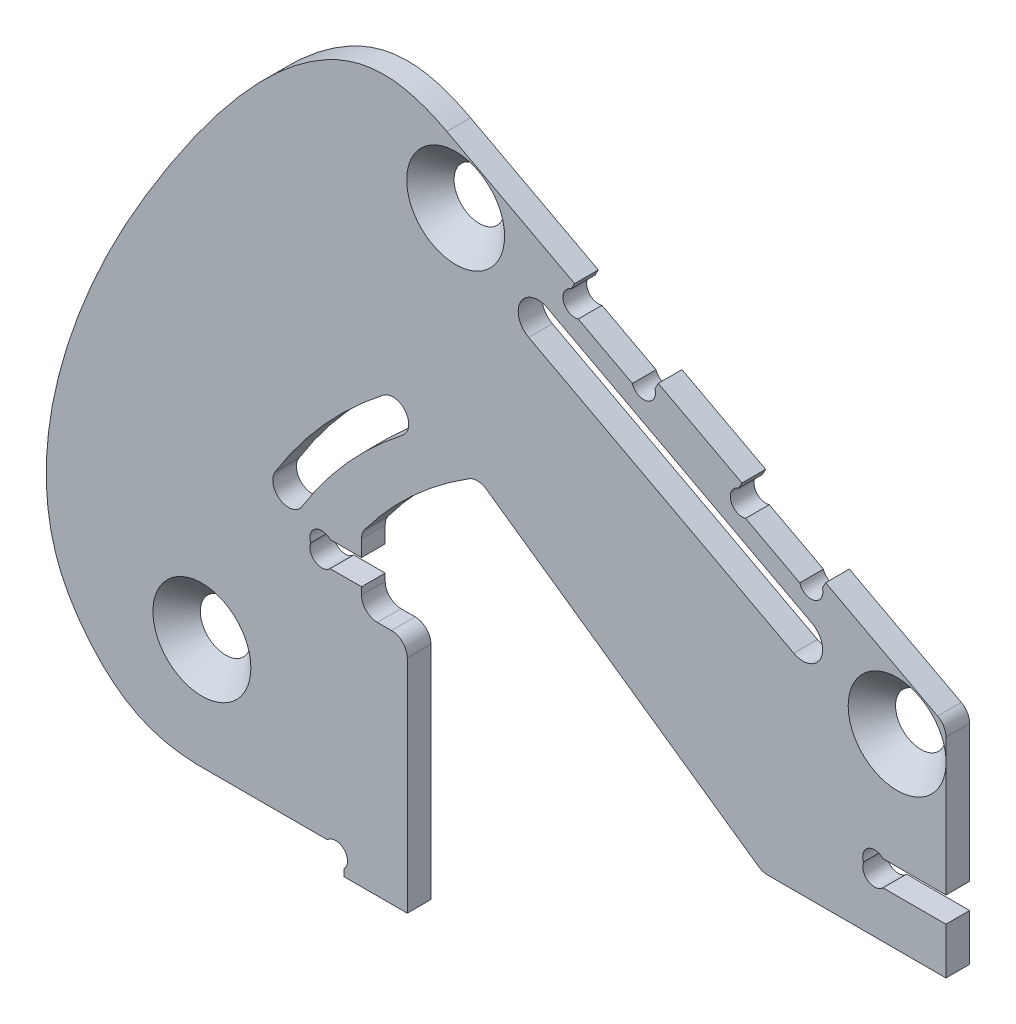
SolidWorks part; units mm, degrees
ref_plane "Front Plane" through (0, 0, 0) normal (0, 0, 1) x (1, 0, 0)
ref_plane "Top Plane" through (0, 0, 0) normal (0, 1, 0) x (1, 0, 0)
ref_plane "Right Plane" through (0, 0, 0) normal (1, 0, 0) x (0, 0, -1)
sketch "Sketch1" plane through (0, 0, 0) normal (0, 0, 1) x (1, 0, 0)
  line L0 (0, 0) -> (-32, 0)
  line L2 (0, 0) -> (2.5, 0)
  line L3 (-1.5, 0) -> (2.5, 0)
  line L4 (-1.5, 0) -> (-1.5, -1.5)
  line L5 (2.5, 0) -> (2.5, 12)
  line L6 (-1.5, -1.5) -> (2.5, -1.5)
  line L7 (-6.1791, 48.5621) -> (62.5843, 12)
  line L8 (62.5843, 12) -> (2.5, 12)
  line L9 (-6.1791, 48.5621) -> (62.5843, 12)
  line L10 (-32, 0) -> (-6.1791, 48.5621)
  line L11 (2.5, 0) -> (2.5, -1.5)
  line L12 (-1.5, 0) -> (2.5, -1.5) construction
  line L13 (-1.5, -1.5) -> (2.5, 0) construction
  point P13 (0.5, -0.75)
  dimension "D1" = 12
  dimension "D2" = 28
  dimension "D3" = 55
  dimension "D4" = 0.5
  dimension "D5" = 32
  dimension "D6" = 4
  dimension "D7" = 1.5
extrude "Base" add sketch "Sketch1" along normal blind 1.5
sketch "Sketch3" plane through (0, 0, 1.5) normal (0, 0, 1) x (1, 0, 0)
  line L0 (62.5843, 12) -> (2.5, 12) construction
  line L1 (25, 12) -> (-3.5, 12)
  line L2 (-0.3961, 13.5) -> (2.5, 13.5)
  line L3 (2.5, 13.5) -> (2.5, 12)
  line L4 (6.9787, 24.6187) -> (25, 12)
  line L5 (2.5, -1.5) -> (2.5, 12) construction
  line L6 (-0.3961, 15) -> (-0.3961, 16.5) construction
  line L7 (-0.3961, 12) -> (-0.3961, 17.9078)
  arc A0 (-3.5, 12) -> (6.9787, 24.6187) centre (19.0917, 3.8998) cw
  point P7 (2.6479, 13.8931)
  line M28 (2.5, 12) -> (62.5843, 12)
  dimension "D3" = 24
  dimension "D1" = 22
  dimension "D2" = 35
  dimension "D4" = 1.5
  dimension "D6" = 28.5
  dimension "D7" = 6
extrude "Camera cut" cut sketch "Sketch3" against normal up to next contours A0 L7 L1 L4 M28
sketch "Sketch4" plane through (0, 0, 1.5) normal (0, 0, 1) x (1, 0, 0)
  line L0 (36.6039, 15) -> (36.6039, 25.814)
  line L1 (-0.3961, 13.5) -> (-0.3961, 17.9078) construction
  line L2 (-6.1791, 48.5621) -> (62.5843, 12) construction
  line L3 (36.6039, 25.814) -> (62.5843, 12)
  line L4 (36.6039, 15) -> (36.6039, 12)
  line L5 (55.3501, 15) -> (1.5, 15) construction
  line L6 (36.6039, 16.5) -> (31.6039, 16.5)
  line L9 (31.6039, 16.5) -> (31.6039, 15)
  line L10 (1.5, 15) -> (-3.5, 15) construction
  line L11 (62.5843, 12) -> (25, 12) construction
  line L12 (31.6039, 15) -> (36.6039, 15)
  line L13 (36.6039, 12) -> (62.5843, 12)
  line L14 (36.6039, 16.55) -> (31.5539, 16.55)
  line L15 (31.5539, 16.55) -> (31.5539, 14.95)
  line L16 (31.5539, 14.95) -> (36.6039, 14.95)
  line L17 (-3.4461, 16.55) -> (-0.3461, 16.55)
  line L18 (-3.3961, 16.5) -> (-0.3961, 16.5)
  line L19 (-3.3961, 16.5) -> (-3.3961, 15)
  line L20 (-3.3961, 15) -> (-0.3961, 15)
  line L21 (-0.3961, 16.5) -> (-0.3961, 15)
  line L22 (-3.3961, 16.5) -> (-0.3961, 15) construction
  line L23 (-3.3961, 15) -> (-0.3961, 16.5) construction
  line L24 (-0.3461, 16.55) -> (-0.3461, 14.95)
  line L25 (-3.4461, 14.95) -> (-0.3461, 14.95)
  line L26 (-3.4461, 16.55) -> (-3.4461, 14.95)
  line L30 (-3.3961, 15) -> (-3.3961, 16.5) construction
  line L31 (1.6039, 16.5) -> (-3.3961, 16.5) construction
  line L32 (55.3501, 16.5) -> (1.6039, 16.5) construction
  line L33 (31.6039, 15) -> (31.6039, 16.5) construction
  point P22 (-1.8961, 15.75)
  line M10 (-0.3961, 13.5) -> (-0.3961, 17.9078)
  arc M11 (-0.3961, 17.9078) -> (6.9787, 24.6187) centre (19.0917, 3.8998) cw
  line M13 (25, 12) -> (62.5843, 12)
  line M14 (62.5843, 12) -> (-6.1791, 48.5621)
  dimension "D1" = 5
  dimension "D2" = 0.05
  dimension "D3" = 0.05
extrude "Top cover sockets" cut sketch "Sketch4" against normal up to next contours L17 L26 L25 L20 L19 L18 M10 M11 | L19 L20 L18 M10 M11 | L0 L4 M13 M14 | L9 L12 L0 L6 | L15 L16 L4 L12 L9 L6 L0 L14
sketch "Sketch5" plane through (0, 0, 1.5) normal (0, 0, 1) x (1, 0, 0)
  line L0 (-7.6814, 45.7367) -> (36.6039, 22.1898) construction
  line L1 (-1.5, 0) -> (-32, 0) construction
  line L2 (5.5628, 38.6946) -> (7.0651, 41.52) construction
  line L3 (-6.1791, 48.5621) -> (36.6039, 25.814) construction
  line L4 (-32, 0) -> (-6.1791, 48.5621) construction
  line L5 (2.5, -1.5) -> (2.5, 13.5) construction
  line L6 (36.6039, 16.55) -> (36.6039, 25.814) construction
  circle A0 centre (5.5628, 38.6946) radius 1.6
  circle A1 centre (33.5136, 23.8329) radius 1.6
  circle A2 centre (-10.5, 7) radius 1.6
  dimension "D2" = 3.2
  dimension "D1" = 3.2
  dimension "D3" = 15
  dimension "D4" = 3.5
  dimension "D5" = 7
  dimension "D6" = 13
extrude "Standoff hole" cut sketch "Sketch5" against normal up to next
sketch "Sketch6" plane through (0, 0, 1.5) normal (0, 0, 1) x (1, 0, 0)
  line L0 (13.094, 38.3144) -> (18.3917, 35.4976)
  line L1 (13.094, 38.3144) -> (12.3898, 36.99)
  line L2 (18.3917, 35.4976) -> (17.6875, 34.1732)
  line L3 (12.3898, 36.99) -> (17.6875, 34.1732)
  line L4 (23.6894, 32.6808) -> (22.9852, 31.3564)
  line L5 (28.2829, 28.5395) -> (22.9852, 31.3564)
  line L6 (28.9871, 29.864) -> (23.6894, 32.6808)
  line L7 (28.9871, 29.864) -> (28.2829, 28.5395)
  line L19 (-6.1791, 48.5621) -> (36.6039, 25.814) construction
  line L21 (5.5628, 38.6946) -> (33.5136, 23.8329) construction
  line L22 (19.5382, 31.2638) -> (21.0405, 34.0892) construction
  line M7 (36.6039, 25.814) -> (-6.1791, 48.5621)
  dimension "D2" = 1.5
  dimension "D3" = 6
  dimension "D1" = 3
extrude "Gopro mount holders" cut sketch "Sketch6" against normal up to next contours L1 L3 L2 M7 | L7 L4 L5 M7
sketch "Sketch9" plane through (0, 0, 0) normal (0, 0, 1) x (1, 0, 0)
  arc A0 (-5.013, 17.9895) -> (1.5924, 25.3509) centre (18.5394, 3.5) cw construction
  arc A1 (0.9795, 26.1411) -> (-5.8647, 18.5135) centre (18.5394, 3.5) ccw
  arc A2 (2.2052, 24.5607) -> (-4.1613, 17.4655) centre (18.5394, 3.5) ccw
  arc A3 (2.2052, 24.5607) -> (0.9795, 26.1411) centre (1.5924, 25.3509) ccw
  arc A4 (-5.8647, 18.5135) -> (-4.1613, 17.4655) centre (-5.013, 17.9895) ccw
  point P3 (-2.0421, 21.9679)
  point P4 (3.4015, 26.6707)
  point P9 (1.5786, 25.3686)
  point P10 (-5.013, 17.9895)
  point P11 (-5.013, 17.9895)
  point P12 (-5.013, 17.9895)
  point P14 (0, 0)
  point P15 (-2.0421, 21.9679)
  dimension "D1" = 9.8904
extrude "Camera angle adjustment cut" cut sketch "Sketch9" along normal up to next contours A4 A1 A3 A2
fillet "Fillet6" radius 1 1 edges at (36.6039, 25.814, 0.75)
sketch "Sketch10" plane through (0, 0, 1.5) normal (0, 0, 1) x (1, 0, 0)
  line L0 (-2.9157, 15.4803) -> (-3.4461, 14.95) construction
  line L1 (-3.4461, 14.95) -> (-0.3961, 14.95) construction
  line L2 (-3.4461, 15.75) -> (-2.2135, 15.75) construction
  line L3 (-3.4461, 16.55) -> (-3.4461, 14.95) construction
  line L4 (13.107, 37.2093) -> (12.3898, 36.99) construction
  line L6 (15.0386, 35.5816) -> (13.7722, 33.1998) construction
  line L7 (21.0405, 34.0892) -> (17.884, 28.1526) construction
  line L9 (31.5539, 15.75) -> (35.7048, 15.75) construction
  line L10 (31.5539, 16.55) -> (31.5539, 14.95) construction
  line L11 (31.5539, 16.55) -> (32.0843, 16.0197) construction
  line L12 (-2.0303, -0.5303) -> (-1.5, 0) construction
  line L13 (-1.5, 0) -> (-32, 0) construction
  line L14 (-1.5, 0) -> (-1.5, -1.5) construction
  line L15 (12.3898, 36.99) -> (17.6875, 34.1732) construction
  line L16 (18.3917, 35.4976) -> (23.6894, 32.6808) construction
  circle A0 centre (-2.9157, 15.4803) radius 0.75
  circle A1 centre (-2.9157, 16.0197) radius 0.75
  circle A2 centre (13.107, 37.2093) radius 0.75
  circle A3 centre (23.7024, 31.5756) radius 0.75
  circle A4 centre (17.4682, 34.8904) radius 0.75
  circle A5 centre (28.0636, 29.2568) radius 0.75
  circle A6 centre (32.0843, 16.0197) radius 0.75
  circle A7 centre (32.0843, 15.4803) radius 0.75
  circle A8 centre (-2.0303, -0.5303) radius 0.75
  dimension "D2" = 45
  dimension "D4" = 1.5
  dimension "D1" = 45
  dimension "D5" = 45
  dimension "D7" = 45
extrude "Milling holes" cut sketch "Sketch10" against normal up to next contours A7 | A6 | A1 | A0 | A2 | A4 | A3 | A5 | A8
sketch "Sketch11" plane through (0, 0, 1.5) normal (0, 0, 1) x (1, 0, 0)
  line L0 (18.3917, 35.4976) -> (23.6894, 32.6808) construction
  line L1 (10.7746, 35.0174) -> (27.5506, 26.0974) construction
  line L2 (11.3615, 36.1211) -> (28.1375, 27.2011)
  line L3 (10.1878, 33.9137) -> (26.9638, 24.9937)
  line L4 (21.0405, 34.0892) -> (18.5758, 29.4537) construction
  arc A2 (11.3615, 36.1211) -> (10.1878, 33.9137) centre (10.7746, 35.0174) ccw
  arc A3 (26.9638, 24.9937) -> (28.1375, 27.2011) centre (27.5506, 26.0974) ccw
  point P8 (19.1626, 30.5574)
  dimension "D1" = 19
  dimension "D2" = 2.5
  dimension "D3" = 4
extrude "Gopro strap" cut sketch "Sketch11" against normal up to next
chamfer "Chamfer1" distance 1.5 angle 45 3 edges at (-8.9, 7, 1.5) (35.1136, 23.8329, 1.5) (7.1628, 38.6946, 1.5)
chamfer "Chamfer2" [suppressed] distance 1.5 angle 45
sketch "Sketch12" plane through (0, 0, 1.5) normal (0, 0, 1) x (1, 0, 0)
  line L0 (-2.5607, 0) -> (-32, 0) construction
  line L2 (-6.1791, 48.5621) -> (13.094, 38.3144) construction
  line L5 (5.0503, 42.5913) -> (-6.1791, 48.5621)
  line L7 (-6.1791, 48.5621) -> (-32, 0)
  line L8 (-32, 0) -> (-9.4561, 0)
  spline S0 degree 3 poles (-9.4561, 0) (-12.3143, -0.0716) (-15.6531, 0.2407) (-22.2188, 9.9898) (-18.9261, 21.1225) (-12.5922, 32.183) (-7.5217, 39.5272) (-0.4789, 44.2751) (2.454, 43.9774) (5.0503, 42.5913) knots 0 0 0 0 0.255853 0.322794 0.630896 0.688625 0.842347 0.875406 1 1 1 1
  point P2 (-11.9795, 37.6531)
  point P4 (-4.4765, 42.924)
  point P8 (-10.5091, 37.6533)
  point P9 (-2.7011, 43.783)
  point P12 (4.0982, 43.0976)
  point P14 (0, 0)
  point P15 (-22.5237, 5.02)
  point P16 (-15.4355, 29.9039)
  point P17 (-20.3118, 5.3216)
  point P18 (-5.5825, 40.511)
  point P19 (-5.8392, 48.3814)
  point P20 (-20.1472, 4.9523)
  point P21 (-19.942, 4.4645)
  point P22 (-9.4561, 0)
  point P26 (-18.4903, 4.5255)
  point P27 (-4.8079, 42.6749)
  point P28 (3.4798, 43.4264)
  point P29 (3.4798, 43.4264)
  point P30 (3.4798, 43.4264)
  point P32 (-3.9107, 42.7038)
  point P33 (5.0503, 42.5913)
  point P34 (-3.4933, 42.2164)
  point P35 (-14.4237, 28.9517)
  point P36 (0, 0)
  line M33 (-6.1791, 48.5621) -> (-32, 0)
  line M34 (-32, 0) -> (-2.5607, 0)
extrude "Front curve" cut sketch "Sketch12" against normal up to next contours S0 L5 M34 M33
fillet "Fillet7" radius 1 5 edges at (25, 12, 0.75) (6.9787, 24.6187, 0.75) (-0.3961, 17.9078, 0.75) (-0.3961, 13.5, 0.75) (2.5, 13.5, 0.75)
